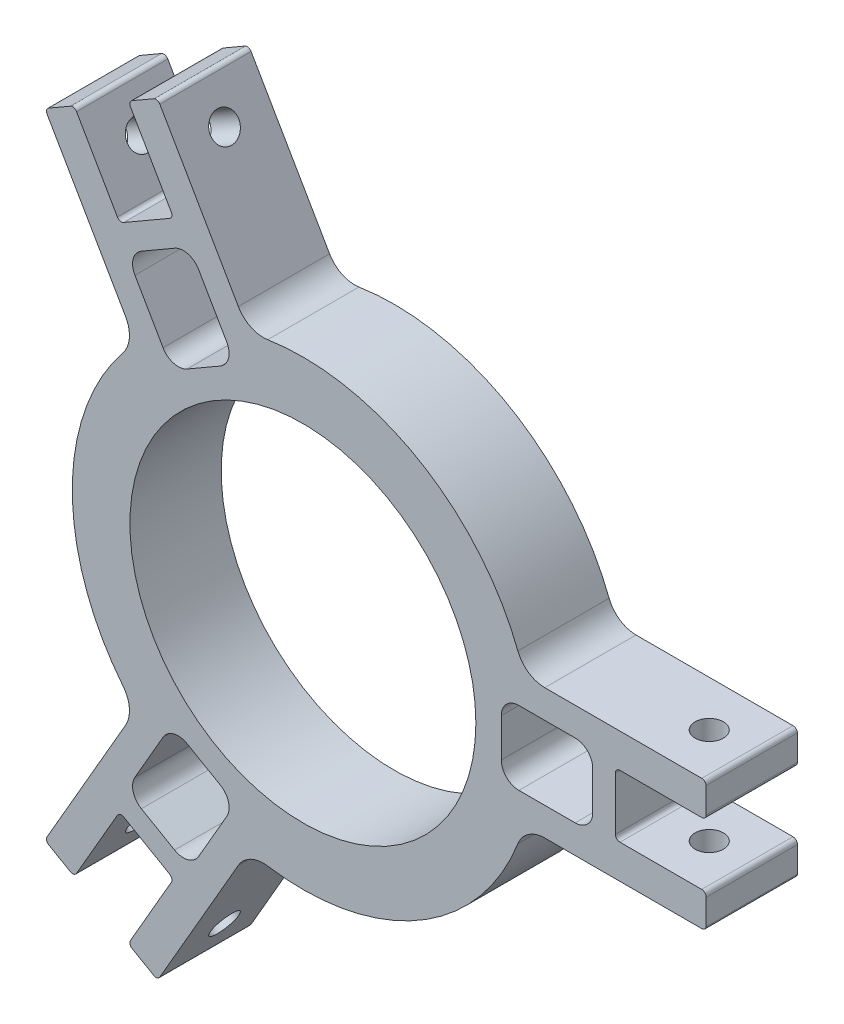
SolidWorks part; units mm, degrees
ref_plane "Front Plane" through (0, 0, 0) normal (0, 0, 1) x (1, 0, 0)
ref_plane "Top Plane" through (0, 0, 0) normal (0, 1, 0) x (1, 0, 0)
ref_plane "Right Plane" through (0, 0, 0) normal (1, 0, 0) x (0, 0, -1)
sketch "Sketch1" plane through (0, 0, 0) normal (0, 0, 1) x (1, 0, 0)
  line L0 (-99.9806, 90.7477) -> (-95.1119, 93.5587)
  line L1 (-100.3466, 89.3817) -> (-91.3466, 73.7932)
  line L2 (-93.873, 93.1308) -> (-76.5831, 63.1838)
  line L6 (-105.2291, 84.1276) -> (-87.7666, 53.8816) construction
  line L8 (-118.7042, 78.7945) -> (-101.4143, 48.8475)
  line L9 (-113.5866, 82.8923) -> (-118.4553, 80.0814)
  line L12 (-112.2205, 82.5263) -> (-103.2205, 66.9379)
  line L13 (-101.8545, 66.5718) -> (-91.7127, 72.4272)
  line L14 (-87.8725, 45.615) -> (-80.5546, 49.84)
  line L15 (-97.9425, 63.0569) -> (-90.6246, 67.2819)
  line L27 (26.4833, 2.023) -> (26.4833, -3.5989)
  line L43 (25.4833, 3.023) -> (7.4833, 3.023)
  line L48 (25.4933, -4.4579) -> (-9.0865, -4.4579)
  line L49 (-96.7836, 69.4995) -> (-94.2836, 65.1694) construction
  line L50 (-2.3917, 1.7784) -> (-14.7819, 1.7784)
  line L51 (-2.3917, 17.9784) -> (-14.7819, 17.9784)
  line L52 (-101.4143, 48.8475) -> (-76.5831, 63.1838) construction
  line L53 (25.4933, 24.2146) -> (-9.0865, 24.2146)
  line L54 (-101.9633, 41.6954) -> (-70.1147, 60.0832) construction
  line L55 (26.4833, 17.7338) -> (26.4833, 23.3557)
  line L56 (-80.5546, 49.84) -> (-90.6246, 67.2819) construction
  line L57 (25.4833, 16.7338) -> (7.4833, 16.7338)
  line L58 (6.4833, 15.7338) -> (6.4833, 4.023)
  line L59 (-18.6569, 14.1034) -> (-18.6569, 5.6534)
  line L60 (1.4833, 14.1034) -> (1.4833, 5.6534)
  line L61 (23.3743, 9.8784) -> (-11.5507, 9.8784) construction
  line L62 (6.4833, 9.8784) -> (1.4833, 9.8784) construction
  line L63 (-9.0865, 24.2146) -> (-9.0865, -4.4579) construction
  line L64 (-15.0059, 28.2662) -> (-15.0059, -8.5094) construction
  line L65 (-113.5866, -63.1356) -> (-118.4553, -60.3247)
  line L66 (-112.2205, -62.7696) -> (-103.2205, -47.1811)
  line L67 (-118.7042, -59.0378) -> (-101.4143, -29.0908)
  line L68 (-99.3609, -38.0068) -> (-93.1658, -27.2766)
  line L69 (-85.3313, -46.1068) -> (-79.1362, -35.3766)
  line L70 (-93.873, -73.3741) -> (-76.5831, -43.4271)
  line L71 (-99.9806, -70.991) -> (-95.1119, -73.802)
  line L72 (-100.3466, -69.625) -> (-91.3466, -54.0365)
  line L73 (-91.7127, -52.6705) -> (-101.8545, -46.8151)
  line L74 (-80.5546, -30.0833) -> (-87.8725, -25.8583)
  line L75 (-90.6246, -47.5252) -> (-97.9425, -43.3002)
  line L76 (-105.2291, -64.3709) -> (-87.7666, -34.1249) construction
  line L77 (-96.7836, -49.7428) -> (-94.2836, -45.4127) construction
  line L78 (-76.5831, -43.4271) -> (-101.4143, -29.0908) construction
  line L79 (-70.1147, -40.3265) -> (-101.9633, -21.9387) construction
  line L80 (-90.6246, 67.2819) -> (-80.5546, 49.84) construction
  line L81 (-85.3313, 65.8635) -> (-79.1362, 55.1334)
  line L82 (-99.3609, 57.7635) -> (-93.1658, 47.0334)
  arc A0 (-76.5831, 63.1838) -> (-70.1147, 60.0832) centre (-71.0838, 66.3588) ccw
  arc A1 (-100.3466, 89.3817) -> (-99.9806, 90.7477) centre (-99.4806, 89.8817) cw
  arc A2 (-93.873, 93.1308) -> (-95.1119, 93.5587) centre (-94.739, 92.6308) ccw
  arc A3 (-91.7127, 72.4272) -> (-91.3466, 73.7932) centre (-92.2127, 73.2932) ccw
  arc A8 (-85.3313, 65.8635) -> (-90.6246, 67.2819) centre (-88.6871, 63.926) ccw
  arc A9 (-79.1362, 55.1334) -> (-80.5546, 49.84) centre (-82.4921, 53.1959) cw
  arc A10 (-99.3609, 57.7635) -> (-97.9425, 63.0569) centre (-96.005, 59.701) cw
  arc A11 (-93.1658, 47.0334) -> (-87.8725, 45.615) centre (-89.81, 48.9709) ccw
  arc A12 (-101.4143, 48.8475) -> (-101.9633, 41.6954) centre (-106.9135, 45.6725) cw
  arc A13 (-118.7042, 78.7945) -> (-118.4553, 80.0814) centre (-117.8381, 79.2945) cw
  arc A14 (-112.2205, 82.5263) -> (-113.5866, 82.8923) centre (-113.0866, 82.0263) ccw
  arc A16 (-101.8545, 66.5718) -> (-103.2205, 66.9379) centre (-102.3545, 67.4379) cw
  circle A49 centre (-62.3613, 9.8784) radius 38.1
  arc A50 (-101.9633, 41.6954) -> (-102.4205, -21.361) centre (-62.3613, 9.8784) ccw
  arc A51 (-14.7724, 27.653) -> (-70.1147, 60.0832) centre (-62.3613, 9.8784) ccw
  arc A53 (-9.0865, -4.4579) -> (-15.0059, -8.5094) centre (-9.0865, -10.8079) ccw
  arc A54 (25.4833, 3.023) -> (26.4833, 2.023) centre (25.4833, 2.023) cw
  arc A55 (25.4933, -4.4579) -> (26.4833, -3.5989) centre (25.4933, -3.4579) ccw
  arc A56 (6.4833, 4.023) -> (7.4833, 3.023) centre (7.4833, 4.023) ccw
  arc A57 (-2.3917, 1.7784) -> (1.4833, 5.6534) centre (-2.3917, 5.6534) ccw
  arc A58 (-14.7819, 1.7784) -> (-18.6569, 5.6534) centre (-14.7819, 5.6534) cw
  arc A59 (-2.3917, 17.9784) -> (1.4833, 14.1034) centre (-2.3917, 14.1034) cw
  arc A60 (-14.7819, 17.9784) -> (-18.6569, 14.1034) centre (-14.7819, 14.1034) ccw
  arc A61 (-9.0865, 24.2146) -> (-15.0059, 28.2662) centre (-9.0865, 30.5646) cw
  arc A62 (25.4933, 24.2146) -> (26.4833, 23.3557) centre (25.4933, 23.2146) cw
  arc A63 (25.4833, 16.7338) -> (26.4833, 17.7338) centre (25.4833, 17.7338) ccw
  arc A64 (6.4833, 15.7338) -> (7.4833, 16.7338) centre (7.4833, 15.7338) cw
  circle A65 centre (-62.3613, 9.8784) radius 38.1
  arc A66 (-15.0059, 28.2662) -> (-69.3857, 60.1904) centre (-62.3613, 9.8784) ccw
  arc A67 (-70.7625, -40.2221) -> (-15.0059, -8.5094) centre (-62.3613, 9.8784) ccw
  arc A68 (-101.4143, -29.0908) -> (-101.9633, -21.9387) centre (-106.9135, -25.9158) ccw
  arc A69 (-112.2205, -62.7696) -> (-113.5866, -63.1356) centre (-113.0866, -62.2696) cw
  arc A70 (-118.7042, -59.0378) -> (-118.4553, -60.3247) centre (-117.8381, -59.5378) ccw
  arc A71 (-101.8545, -46.8151) -> (-103.2205, -47.1811) centre (-102.3545, -47.6811) ccw
  arc A72 (-99.3609, -38.0068) -> (-97.9425, -43.3002) centre (-96.005, -39.9443) ccw
  arc A73 (-93.1658, -27.2766) -> (-87.8725, -25.8583) centre (-89.81, -29.2141) cw
  arc A74 (-85.3313, -46.1068) -> (-90.6246, -47.5252) centre (-88.6871, -44.1693) cw
  arc A75 (-79.1362, -35.3766) -> (-80.5546, -30.0833) centre (-82.4921, -33.4391) ccw
  arc A76 (-76.5831, -43.4271) -> (-70.1147, -40.3265) centre (-71.0838, -46.6021) cw
  arc A77 (-93.873, -73.3741) -> (-95.1119, -73.802) centre (-94.739, -72.8741) cw
  arc A78 (-100.3466, -69.625) -> (-99.9806, -70.991) centre (-99.4806, -70.125) ccw
  arc A79 (-91.7127, -52.6705) -> (-91.3466, -54.0365) centre (-92.2127, -53.5365) cw
  circle A80 centre (-62.3613, 9.8784) radius 38.1
  arc A81 (-70.1147, -40.3265) -> (-15.2776, -9.1943) centre (-62.3613, 9.8784) ccw
  arc A82 (-101.549, 42.2043) -> (-101.9633, -21.9387) centre (-62.3613, 9.8784) ccw
  point P135 (-62.3613, 9.8784)
  dimension "D5" = 1
  dimension "D6" = 1
  dimension "D17" = 50.8
  dimension "D33" = 6.35
  dimension "D1" = 5.6219
  dimension "D2" = 90
  dimension "D3" = 18
  dimension "D4" = 90
  dimension "D7" = 1
  dimension "1" = 1
  dimension "D8" = 3
  dimension "D16" = 43.7044
  dimension "D38" = 28.6726
  dimension "D48" = 34.5798
  dimension "5" = 5
extrude "Boss-Extrude1" add sketch "Sketch1" along normal blind 20.1 contours A50 A82 A68 L67 A70 L65 A69 L66 A71 L73 A79 L72 A78 L71 A77 L70 A76 A67 A53 L48 A55 L27 A54 L43 A56 L58 A64 L57 A63 L55 A62 L53 A61 A51 A0 L2 A2 L0 A1 L1 A3 L13 A16 L12 A14 region at (-96.4375, 90.2327, 0)
sketch "Sketch4" plane through (-30.0779, -17.3655, 0) normal (0.866, 0.5, 0) x (0, 0, -1)
  line L0 (-20.1, 127.5901) -> (0, 127.5901) construction
  line L2 (-10.05, 127.5901) -> (-10.05, 93.0103) construction
  line L3 (-20.1, 93.0103) -> (0, 93.0103) construction
  circle A0 centre (-10.05, 119.1901) radius 3.125
  point P8 (0, 0)
  dimension "D1" = 8.4
  dimension "D3" = 6.25
extrude "Cut-Extrude3" cut sketch "Sketch4" against normal through all
ref_plane "Plane1" through (-95.1119, 93.5587, 20.1) normal (0, 0, -1) x (-1, 0, 0)
sketch "Sketch6" plane through (-38.6328, 22.3047, 0) normal (0.866, -0.5, 0) x (0, 0, -1)
  line L0 (-10.05, -75.9005) -> (-10.05, -110.4803) construction
  line L1 (-20.1, -110.4803) -> (0, -110.4803) construction
  line L2 (-20.1, -75.9005) -> (0, -75.9005) construction
  circle A0 centre (-10.05, -102.0803) radius 3.125
  dimension "D1" = 6.25
  dimension "D2" = 8.4
extrude "Cut-Extrude4" cut sketch "Sketch6" against normal through all
sketch "Sketch7" plane through (0, 24.2146, 0) normal (0, 1, 0) x (1, 0, 0)
  line L0 (25.4933, -20.1) -> (25.4933, 0) construction
  line L1 (-9.0865, -10.05) -> (25.4933, -10.05) construction
  line L2 (-9.0865, -20.1) -> (-9.0865, 0) construction
  circle A0 centre (17.0933, -10.05) radius 3.125
  dimension "D1" = 6.25
  dimension "8.4" = 8.4
extrude "Cut-Extrude5" cut sketch "Sketch7" against normal through all
